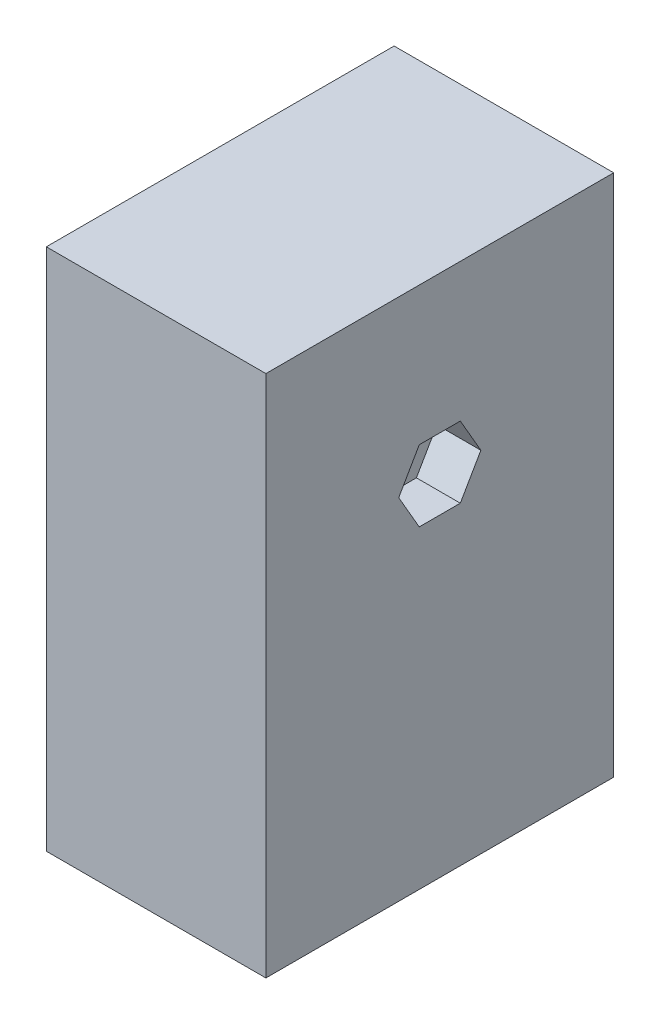
SolidWorks part; units mm, degrees
ref_plane "Płaszczyzna przednia" through (0, 0, 0) normal (0, 0, 1) x (1, 0, 0)
ref_plane "Płaszczyzna górna" through (0, 0, 0) normal (0, 1, 0) x (1, 0, 0)
ref_plane "Płaszczyzna prawa" through (0, 0, 0) normal (1, 0, 0) x (0, 0, -1)
sketch "Sketch1" plane through (0, 0, 0) normal (1, 0, 0) x (0, 0, -1)
  line L1 (-19.8, 29.8) -> (19.8, 29.8)
  line L2 (-19.8, 29.8) -> (-19.8, -29.8)
  line L3 (-19.8, -29.8) -> (19.8, -29.8)
  line L4 (19.8, 29.8) -> (19.8, -29.8)
  line L5 (-19.8, 29.8) -> (19.8, -29.8) construction
  line L6 (-19.8, -29.8) -> (19.8, 29.8) construction
  point P0 (0, 0)
  dimension "D1" = 39.6
  dimension "D2" = 59.6
extrude "Boss-Extrude1" add sketch "Sketch1" along normal blind 25
sketch "Sketch2" plane through (0, 0, 0) normal (1, 0, 0) x (0, 0, -1)
  line L0 (-19.8, 29.8) -> (-19.8, -29.8) construction
  line L2 (4.6765, 10) -> (2.3383, 14.05)
  line L3 (2.3383, 14.05) -> (-2.3383, 14.05)
  line L4 (-2.3383, 14.05) -> (-4.6765, 10)
  line L5 (-4.6765, 10) -> (-2.3383, 5.95)
  line L6 (-2.3383, 5.95) -> (2.3383, 5.95)
  line L7 (2.3383, 5.95) -> (4.6765, 10)
  circle A0 centre (0, 10) radius 4.05 construction
  point P1 (0, 0)
  point P2 (0, 7.6233)
  dimension "D1" = 8.1
  dimension "D2" = 10
  dimension "D3" = 19.8
extrude "Cut-Extrude1" cut sketch "Sketch2" along normal blind 5
sketch "Sketch3" plane through (0, 0, 0) normal (1, 0, 0) x (0, 0, -1)
  line L2 (-19.8, 29.8) -> (-19.8, -29.8) construction
  circle A0 centre (0, 10) radius 2.75
  point P3 (0, 0)
  point P4 (0, 8.8631)
  point P8 (0, 0)
  dimension "D1" = 5.5
  dimension "D3" = 19.8
  dimension "D2" = 10
extrude "Cut-Extrude2" cut sketch "Sketch3" against normal through all and the other way through all
extrude "Cut-Extrude4" cut sketch "Sketch2<2>" against normal blind 5 from surface starting at face at (25, 10, -2.75)
sketch "Sketch2<2>" plane through (0, 0, 0) normal (1, 0, 0) x (0, 0, -1) same geometry as "Sketch2"
